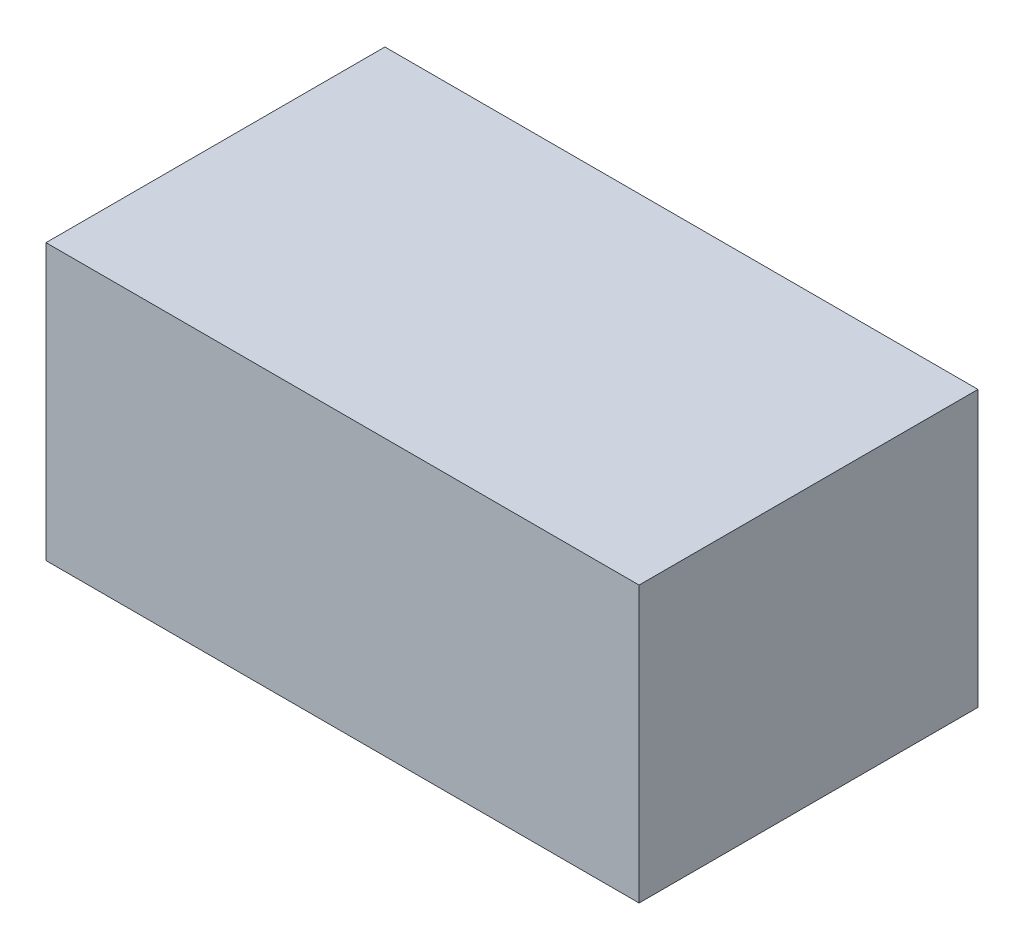
SolidWorks part; units mm, degrees
material "PTFE (general)"
ref_plane "Front Plane" through (0, 0, 0) normal (0, 0, 1) x (1, 0, 0)
ref_plane "Top Plane" through (0, 0, 0) normal (0, 1, 0) x (1, 0, 0)
ref_plane "Right Plane" through (0, 0, 0) normal (1, 0, 0) x (0, 0, -1)
sketch "Sketch1" plane through (0, 0, 0) normal (0, 1, 0) x (1, 0, 0)
  line L1 (-70, 40) -> (70, 40)
  line L2 (-70, 40) -> (-70, -40)
  line L3 (-70, -40) -> (70, -40)
  line L4 (70, 40) -> (70, -40)
  dimension "D1" = 40
  dimension "D2" = 40
  dimension "D3" = 70
  dimension "D4" = 70
  dimension "D5" = 140
extrude "Boss-Extrude1" add sketch "Sketch1" along normal blind 65
